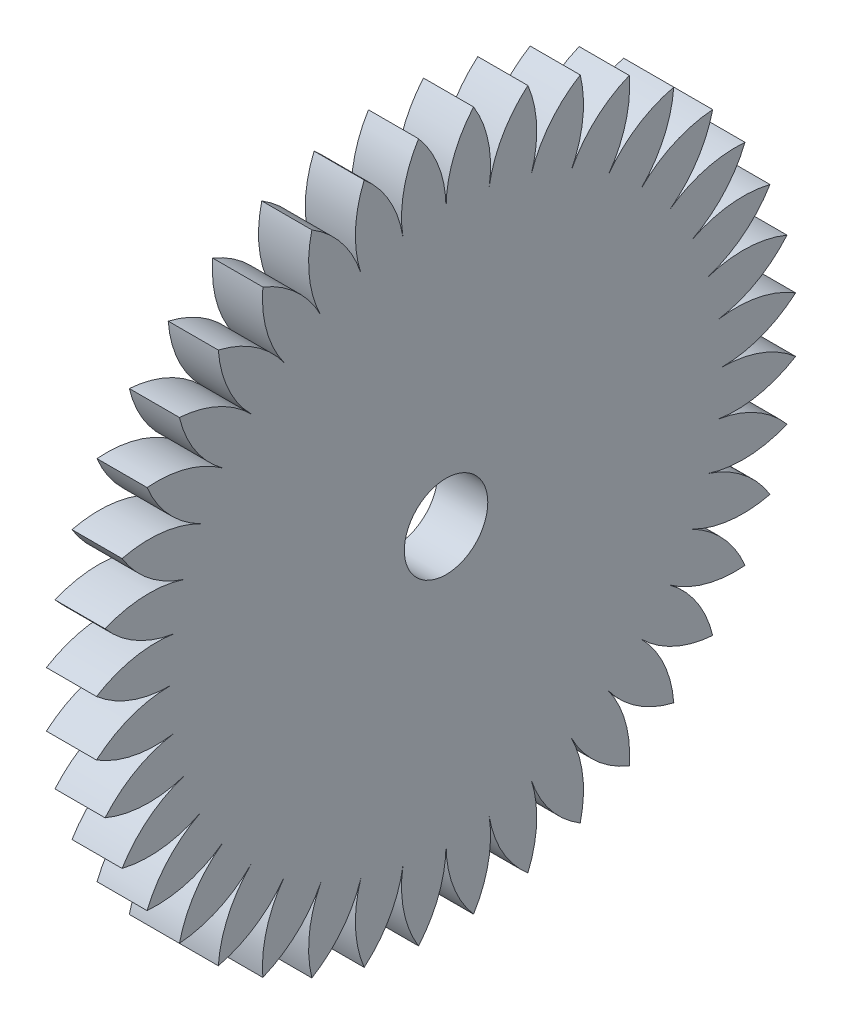
SolidWorks part; units mm, degrees
ref_plane "Front Plane" through (0, 0, 0) normal (0, 0, 1) x (1, 0, 0)
ref_plane "Top Plane" through (0, 0, 0) normal (0, 1, 0) x (1, 0, 0)
ref_plane "Right Plane" through (0, 0, 0) normal (1, 0, 0) x (0, 0, -1)
sketch "Sketch1" plane through (0, 0, 0) normal (1, 0, 0) x (0, 0, -1)
  line L0 (0, 16.5) -> (0, 0)
  line L5 (0, 0) -> (2.5812, 16.2969)
  arc A1 (0, 16.5) -> (1.6476, 20.9353) centre (6.7934, 16.5) cw
  arc A2 (1.6476, 20.9353) -> (2.5812, 16.2969) centre (-4.1286, 17.3596) cw
  dimension "D2" = 21
  dimension "D1" = 16.5
  dimension "D3" = 9
extrude "Boss-Extrude1" add sketch "Sketch1" along normal blind 3 contours A2 A1 region at (0, 13.0109, -1.024)
pattern_circular "CirPattern1" count 40 over 360 about axis through (3, 0, 0) along (-1, 0, 0) of "Boss-Extrude1"
sketch "Sketch2" plane through (0, 0, 0) normal (1, 0, 0) x (0, 0, -1)
  circle A0 centre (0, 0) radius 2.5
  dimension "D1" = 5
extrude "Cut-Extrude2" cut sketch "Sketch2" along normal through all
